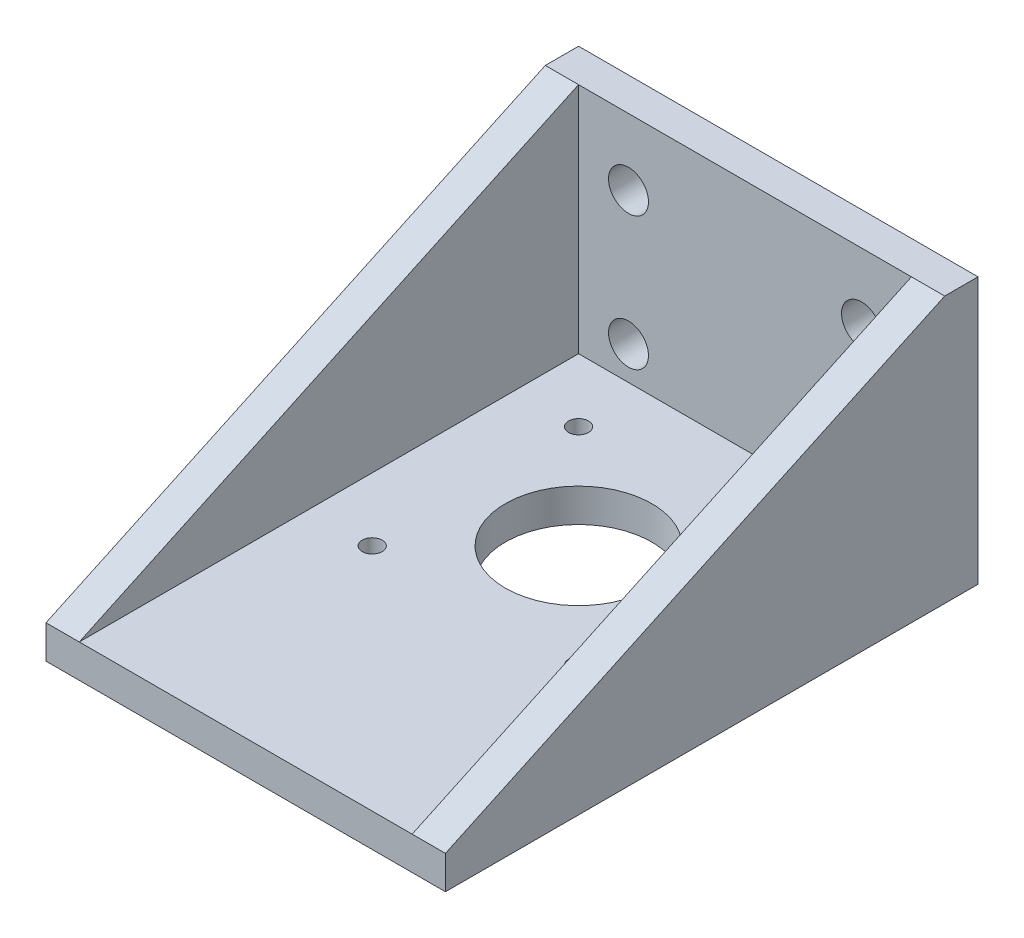
SolidWorks part; units mm, degrees
ref_plane "Спереди" through (0, 0, 0) normal (0, 0, 1) x (1, 0, 0)
ref_plane "Сверху" through (0, 0, 0) normal (0, 1, 0) x (1, 0, 0)
ref_plane "Справа" through (0, 0, 0) normal (1, 0, 0) x (0, 0, -1)
sketch "Эскиз1" plane through (0, 0, 0) normal (0, 1, 0) x (1, 0, 0)
  line L0 (30, 80) -> (30, 0) construction
  line L1 (0, 0) -> (60, 0)
  line L2 (0, 0) -> (0, 80)
  line L3 (0, 80) -> (60, 80)
  line L4 (60, 0) -> (60, 80)
  line L5 (19, 50) -> (41, 50) construction
  circle A0 centre (30, 50) radius 11
  circle A1 centre (14.5, 65.5) radius 1.5
  circle A2 centre (45.5, 65.5) radius 1.5
  circle A3 centre (45.5, 34.5) radius 1.5
  circle A4 centre (14.5, 34.5) radius 1.5
  dimension "D5" = 3
  dimension "D7" = 22
  dimension "D1" = 80
  dimension "D2" = 60
  dimension "D3" = 31
  dimension "D4" = 31
  dimension "D6" = 50
extrude "Бобышка-Вытянуть1" add sketch "Эскиз1" along normal blind 5
sketch "Эскиз3" plane through (0, 5, 0) normal (0, 1, 0) x (1, 0, 0)
  line L0 (5, 75) -> (55, 75)
  line L1 (55, 75) -> (55, 0)
  line L2 (0, 0) -> (60, 0) construction
  line L3 (55, 0) -> (60, 0)
  line L4 (60, 0) -> (60, 80)
  line L5 (60, 80) -> (0, 80)
  line L6 (0, 80) -> (0, 0)
  line L7 (0, 0) -> (5, 0)
  line L8 (5, 0) -> (5, 75)
  dimension "D1" = 5
  dimension "D2" = 5
  dimension "D3" = 5
  dimension "D4" = 75
extrude "Бобышка-Вытянуть2" add sketch "Эскиз3" along normal blind 35
sketch "Эскиз4" plane through (0, 0, -80) normal (0, 0, -1) x (-1, 0, 0)
  line L0 (-30, 0) -> (-30, 40) construction
  line L1 (-60, 0) -> (0, 0) construction
  line L2 (-60, 40) -> (0, 40) construction
  line L3 (0, 10) -> (-60, 10) construction
  line L4 (0, 40) -> (0, 0) construction
  line L5 (-60, 40) -> (-60, 0) construction
  line L6 (-60, 30) -> (0, 30) construction
  circle A0 centre (-12.5, 10) radius 3
  circle A1 centre (-12.5, 30) radius 3
  circle A2 centre (-47.5, 30) radius 3
  circle A3 centre (-47.5, 10) radius 3
  dimension "D3" = 6
  dimension "D1" = 10
  dimension "D2" = 10
  dimension "D4" = 35
  dimension "D5" = 35
extrude "Вырез-Вытянуть1" cut sketch "Эскиз4" against normal up to surface (5 mm away) up to face at (30, 22.5, -75)
sketch "Эскиз5" plane through (0, 0, 0) normal (-1, 0, 0) x (0, 0, 1)
  line L0 (0, 5) -> (-75, 40)
  line L1 (0, 40) -> (0, 0) construction
  line L2 (-80, 40) -> (0, 40) construction
  line L3 (-75, 40) -> (0, 40)
  line L4 (0, 40) -> (0, 5)
  line L5 (-80, 0) -> (0, 0) construction
  line L6 (-80, 40) -> (-80, 0) construction
  dimension "D1" = 5
  dimension "D2" = 5
extrude "Вырез-Вытянуть2" cut sketch "Эскиз5" against normal up to surface (60 mm away) up to face at (60, 20, -40)
